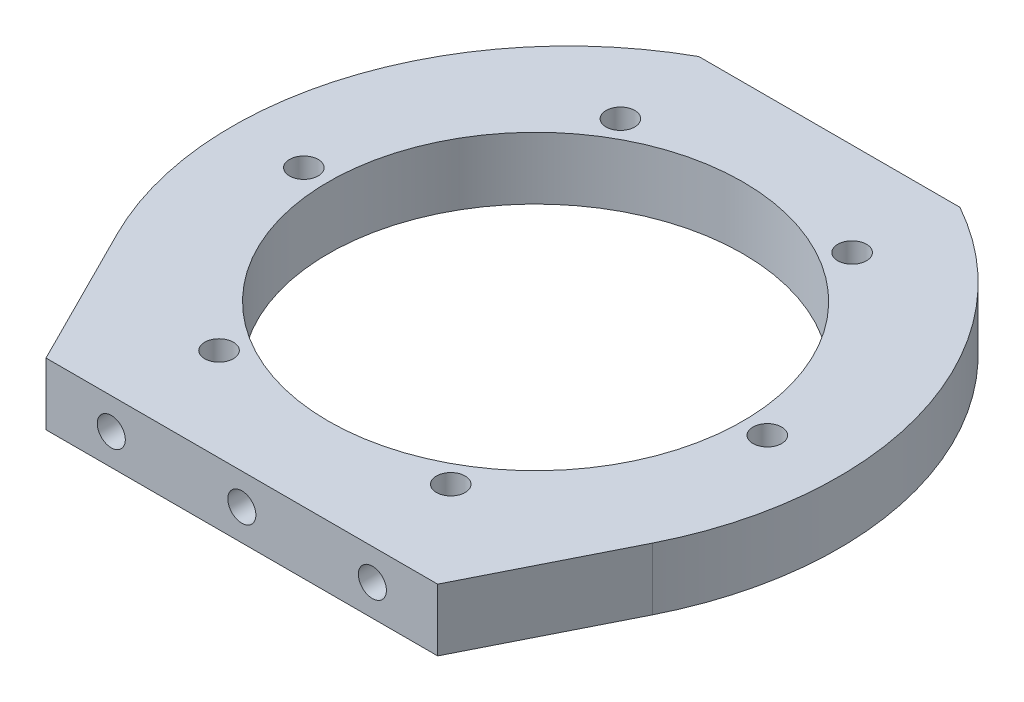
SolidWorks part; units mm, degrees
material "6061 Alloy"
ref_plane "Front Plane" through (0, 0, 0) normal (0, 0, 1) x (1, 0, 0)
ref_plane "Top Plane" through (0, 0, 0) normal (0, 1, 0) x (1, 0, 0)
ref_plane "Right Plane" through (0, 0, 0) normal (1, 0, 0) x (0, 0, -1)
sketch "Sketch1" plane through (0, 0, 0) normal (0, 1, 0) x (1, 0, 0)
  line L5 (0, 0) -> (0, -45) construction
  line L6 (-30, -45) -> (30, -45)
  line L7 (-20, 45) -> (20, 45)
  line L8 (0, 45) -> (0, 0) construction
  line L9 (-40.9978, -23.1128) -> (-30, -45)
  line L11 (5, 0) -> (0, 0) construction
  line L12 (40.9978, -23.1128) -> (30, -45)
  circle A2 centre (0, 0) radius 39.5 construction
  arc A5 (-20, 45) -> (-40.9978, -23.1128) centre (5, 0) ccw
  arc A6 (20, 45) -> (40.9978, -23.1128) centre (-5, 0) cw
  dimension "D1" = 45
  dimension "D3" = 45
  dimension "D4" = 40
  dimension "D2" = 79
  dimension "D6" = 5
  dimension "D5" = 60
extrude "3/8inch" add sketch "Sketch1" along normal mid plane 9.525
sketch "Sketch2" plane through (0, 4.7625, 0) normal (0, 1, 0) x (1, 0, 0)
  circle A0 centre (0, 0) radius 31.75
  dimension "D1" = 63.5
extrude "Cut-Extrude1" cut sketch "Sketch2" against normal up to surface (9.525 mm away) up to face at (0, -4.7625, 6.297)
sketch "Sketch3" plane through (0, 4.7625, 0) normal (0, 1, 0) x (1, 0, 0)
  line L0 (17.75, 30.7439) -> (0, 0) construction
  line L1 (20, 45) -> (-20, 45) construction
  circle A0 centre (0, 0) radius 35.5 construction
  circle A1 centre (17.75, 30.7439) radius 2.2
  circle A2 centre (35.5, 0) radius 2.2
  circle A3 centre (17.75, -30.7439) radius 2.2
  circle A4 centre (-17.75, -30.7439) radius 2.2
  circle A5 centre (-35.5, 0) radius 2.2
  circle A6 centre (-17.75, 30.7439) radius 2.2
  point P17 (0, 0)
  dimension "D1" = 71
  dimension "D2" = 4.4
  dimension "D4" = 120
  dimension "D3" = 6
extrude "M4_through" cut sketch "Sketch3" against normal up to surface (9.525 mm away) up to face at (0, -4.7625, -31.75)
sketch "Sketch4" plane through (0, 0, -45) normal (0, 0, -1) x (-1, 0, 0)
  line L0 (0, -4.7625) -> (0, 4.7625) construction
  line L1 (-20, 4.7625) -> (20, 4.7625) construction
  line L2 (0, 0) -> (-12, 0) construction
  line L3 (-20, -4.7625) -> (20, -4.7625) construction
  circle A0 centre (-12, 0) radius 2.15
  circle A1 centre (12, 0) radius 2.15
  dimension "D1" = 4.3
  dimension "D2" = 12
extrude "M5x8_DRILL" cut sketch "Sketch4" against normal blind 8
sketch "Sketch5" plane through (0, 0, 45) normal (0, 0, 1) x (1, 0, 0)
  line L0 (0, -4.7625) -> (0, 4.7625) construction
  line L1 (-30, 4.7625) -> (30, 4.7625) construction
  line L2 (0, 0) -> (-20, 0) construction
  line L3 (-30, -4.7625) -> (30, -4.7625) construction
  circle A0 centre (-20, 0) radius 2.15
  circle A1 centre (20, 0) radius 2.15
  circle A2 centre (0, 0) radius 2.15
  dimension "D1" = 4.3
  dimension "D2" = 20
extrude "M5x8_DRILL2" cut sketch "Sketch5" against normal blind 8
